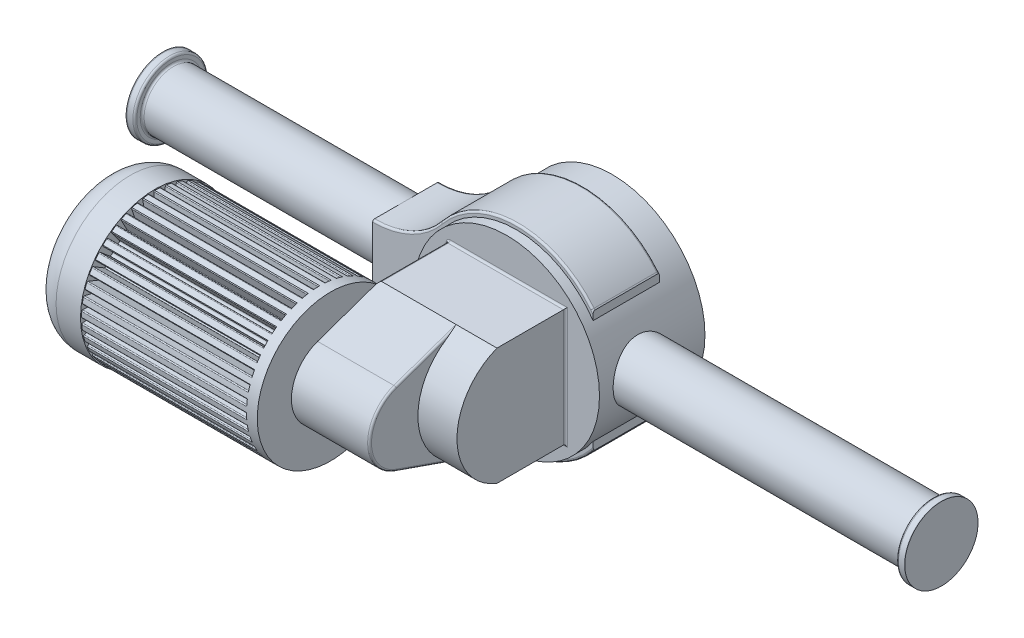
SolidWorks part; units mm, degrees
ref_plane "Front Plane" through (0, 0, 0) normal (0, 0, 1) x (1, 0, 0)
ref_plane "Top Plane" through (0, 0, 0) normal (0, 1, 0) x (1, 0, 0)
ref_plane "Right Plane" through (0, 0, 0) normal (1, 0, 0) x (0, 0, -1)
sketch "Sketch1" plane through (0, 0, 0) normal (0, 0, 1) x (1, 0, 0)
  line L0 (-400, 0) -> (-400, 37.5)
  line L1 (55, 0) -> (-55, 0) construction
  line L2 (-400, 37.5) -> (-390, 37.5)
  line L3 (-390, 37.5) -> (-390, 30)
  line L4 (-390, 30) -> (390, 30)
  line L5 (0, -55) -> (0, 55) construction
  line L6 (390, 37.5) -> (390, 30)
  line L7 (400, 37.5) -> (390, 37.5)
  line L8 (400, 0) -> (400, 37.5)
  line L9 (-87.9629, 0) -> (63.6317, 0) construction
  line L10 (-400, 0) -> (400, 0)
  point P8 (0, 30)
  dimension "D1" = 10
  dimension "D2" = 37.5
  dimension "D3" = 30
  dimension "D4" = 400
revolve "Revolve1" add sketch "Sketch1" angle 360 about L9
sketch "Sketch2" plane through (-400, 0, 0) normal (-1, 0, 0) x (0, 0, 1)
  line L1 (-40, -40) -> (40, -40)
  line L2 (-40, -40) -> (-40, 40)
  line L3 (-40, 40) -> (40, 40)
  line L4 (40, -40) -> (40, 40)
  line L5 (-40, -40) -> (40, 40) construction
  line L6 (-40, 40) -> (40, -40) construction
  point P0 (0, 0)
  dimension "D1" = 80
  dimension "D2" = 80
extrude "Boss-Extrude1" add sketch "Sketch2" along normal blind 10
mirror "Mirror1" about plane through (0, 0, 0) normal (1, 0, 0) of "Boss-Extrude1"
sketch "Sketch3" plane through (0, 0, 0) normal (0, 0, 1) x (1, 0, 0)
  line L0 (44, 0) -> (-44, 0) construction
  line L2 (390, 30) -> (-390, 30) construction
  line L3 (-150, 30) -> (-150, -30)
  line L4 (75.7697, 62.0357) -> (75.7697, -62.0357)
  line L5 (-410, -40) -> (-410, 40) construction
  arc A0 (-80.222, -63.1579) -> (74.8404, -63.1579) centre (-2.6908, 0) ccw
  arc A1 (-150, 30) -> (-80.222, 63.1579) centre (-150, 120) ccw
  arc A2 (74.8404, 63.1579) -> (75.7697, 62.0357) centre (144.6184, 120) ccw
  arc A3 (74.8404, -63.1579) -> (75.7697, -62.0357) centre (144.6184, -120) cw
  arc A4 (-150, -30) -> (-80.222, -63.1579) centre (-150, -120) cw
  arc A5 (74.8404, 63.1579) -> (-80.222, 63.1579) centre (-2.6908, 0) ccw
  point P12 (-80.222, 63.1579)
  point P13 (-150, 30)
  point P20 (75.7697, 0)
  point P25 (-150, 0)
  dimension "D1" = 260
  dimension "D2" = 200
  dimension "D3" = 180
  dimension "D4" = 180
extrude "Boss-Extrude2" add sketch "Sketch3" along normal blind 34 and the other way blind 34 contours A5 A1 L3 A4 A0 A3 L4 A2
sketch "Sketch6" plane through (0, 0, 0) normal (0, 0, 1) x (1, 0, 0)
  circle A0 centre (-2.6908, 0) radius 95
extrude "Boss-Extrude3" add sketch "Sketch6" along normal blind 44 and the other way blind 64
sketch "Sketch7" plane through (0, 0, 0) normal (0, 1, 0) x (1, 0, 0)
  line L0 (115.6, 64) -> (115.6, -44) construction
  line L1 (92.3092, 64) -> (-97.6908, 64) construction
  line L2 (-97.6908, -44) -> (92.3092, -44) construction
  line L3 (115.6, 64) -> (115.6, 89.5157)
  line L4 (115.6, 64) -> (210.6, 64)
  arc A0 (115.6, 89.5157) -> (210.6, 64) centre (115.6, -100.0943) cw
sketch "Sketch8" plane through (0, 0, 44) normal (0, 0, 1) x (1, 0, 0)
  line L1 (-62.6908, -60) -> (57.3092, -60)
  line L2 (-62.6908, -60) -> (-62.6908, 60)
  line L3 (-62.6908, 60) -> (57.3092, 60)
  line L4 (57.3092, -60) -> (57.3092, 60)
  line L5 (-62.6908, -60) -> (57.3092, 60) construction
  line L6 (-62.6908, 60) -> (57.3092, -60) construction
  point P0 (-2.6908, 0)
  dimension "D1" = 120
  dimension "D2" = 120
extrude "Boss-Extrude4" add sketch "Sketch8" along normal blind 70
sketch "Sketch9" plane through (-62.6908, 0, 0) normal (-1, 0, 0) x (0, 0, 1)
  line L0 (114, 60) -> (114, -60)
  arc A0 (114, 60) -> (114, -60) centre (90.5319, 0) cw
extrude "Boss-Extrude5" add sketch "Sketch9" along direction (-1, 0, 0) on the side against the normal up to surface (120 mm away)
sketch "Sketch10" plane through (-62.6908, 0, 0) normal (-1, 0, 0) x (0, 0, 1)
  line L0 (181.4821, 0) -> (-181.4821, 0) construction
  line L1 (114, 60) -> (177.6461, 37.7612)
  line L2 (114, -60) -> (177.6461, -37.7612)
  line L3 (114, 60) -> (114, -60)
  arc A0 (177.6461, -37.7612) -> (177.6461, 37.7612) centre (164.4519, 0) ccw
  dimension "D1" = 40
extrude "Boss-Extrude6" add sketch "Sketch10" against normal blind 80
sketch "Sketch12" plane through (-62.6908, 0, 0) normal (-1, 0, 0) x (0, 0, 1)
  circle A0 centre (164.4519, 0) radius 75
  arc A1 (177.6461, -37.7612) -> (177.6461, 37.7612) centre (164.4519, 0) ccw construction
  dimension "D1" = 150
extrude "Boss-Extrude7" add sketch "Sketch12" along normal blind 180
sketch "Sketch16" plane through (-242.6908, 0, 0) normal (-1, 0, 0) x (0, 0, 1)
  line L3 (165.1686, 74.0313) -> (165.0485, 61.627)
  line L4 (169.9676, 73.8009) -> (168.8566, 61.2216)
  line L5 (164.4519, 75) -> (164.4519, 75.6111)
  line L6 (164.4519, 75.6111) -> (169.6116, 75.2904)
  line L7 (169.6116, 75.2904) -> (171.0517, 75.2904)
  line L8 (171.0517, 75.2904) -> (171.0517, 74.7091)
  line L9 (176.7408, 73.0077) -> (174.6818, 60.7749)
  line L10 (176.1845, 74.0766) -> (176.2801, 74.6802)
  line L11 (176.2801, 74.6802) -> (181.3261, 73.5563)
  line L12 (181.3261, 73.5563) -> (182.7485, 73.331)
  line L13 (182.7485, 73.331) -> (182.6575, 72.7568)
  line L14 (181.4447, 72.0295) -> (178.3795, 59.7788)
  line L15 (188.0105, 70.1864) -> (184.0631, 58.4264)
  line L16 (187.6281, 71.3292) -> (187.817, 71.9105)
  line L17 (187.817, 71.9105) -> (192.6251, 70.011)
  line L18 (192.6251, 70.011) -> (193.9947, 69.566)
  line L19 (193.9947, 69.566) -> (193.815, 69.0131)
  line L20 (192.5034, 68.4844) -> (187.5595, 56.8641)
  line L21 (198.7, 65.6369) -> (192.9616, 54.6392)
  line L22 (198.5012, 66.8255) -> (198.7786, 67.37)
  line L23 (198.7786, 67.37) -> (203.2304, 64.7418)
  line L24 (203.2304, 64.7418) -> (204.5135, 64.088)
  line L25 (204.5135, 64.088) -> (204.2496, 63.57)
  line L26 (202.8713, 63.253) -> (196.1705, 52.5491)
  line L27 (208.5462, 59.4712) -> (201.158, 49.5066)
  line L28 (208.5358, 60.6763) -> (208.895, 61.1707)
  line L29 (208.895, 61.1707) -> (212.8808, 57.8784)
  line L30 (212.8808, 57.8784) -> (214.0458, 57.0319)
  line L31 (214.0458, 57.0319) -> (213.7041, 56.5616)
  line L32 (212.2933, 56.4641) -> (204.0005, 46.9403)
  line L33 (217.3067, 51.8412) -> (208.4506, 43.155)
  line L34 (217.4849, 53.033) -> (217.917, 53.4651)
  line L35 (217.917, 53.4651) -> (221.3387, 49.5899)
  line L36 (221.3387, 49.5899) -> (222.357, 48.5716)
  line L37 (222.357, 48.5716) -> (221.9459, 48.1605)
  line L38 (220.5372, 48.2849) -> (210.8566, 40.1756)
  line L39 (224.7657, 42.9346) -> (214.6599, 35.7407)
  line L40 (225.1281, 44.0839) -> (225.6226, 44.4431)
  line L41 (225.6226, 44.4431) -> (228.3959, 40.0803)
  line L42 (228.3959, 40.0803) -> (229.2424, 38.9152)
  line L43 (229.2424, 38.9152) -> (228.772, 38.5735)
  line L44 (227.4001, 38.9168) -> (216.5702, 32.4217)
  line L45 (230.7396, 32.9709) -> (219.6328, 27.4464)
  line L46 (231.2774, 34.0493) -> (231.8219, 34.3267)
  line L47 (231.8219, 34.3267) -> (233.8786, 29.5838)
  line L48 (233.8786, 29.5838) -> (234.5324, 28.3006)
  line L49 (234.5324, 28.3006) -> (234.0144, 28.0367)
  line L50 (232.713, 28.5904) -> (221.0004, 23.8694)
  line L51 (235.0813, 22.1952) -> (223.247, 18.4763)
  line L52 (235.7811, 23.1763) -> (236.3623, 23.3651)
  line L53 (236.3623, 23.3651) -> (237.6517, 18.3588)
  line L54 (237.6517, 18.3588) -> (238.0967, 16.9892)
  line L55 (238.0967, 16.9892) -> (237.5439, 16.8096)
  line L56 (236.3452, 17.56) -> (224.0382, 14.7294)
  line L57 (237.6838, 10.8731) -> (225.4135, 9.0513)
  line L58 (238.5285, 11.7326) -> (239.1321, 11.8282)
  line L59 (239.1321, 11.8282) -> (239.6225, 6.6818)
  line L60 (239.6225, 6.6818) -> (239.8477, 5.2594)
  line L61 (239.8477, 5.2594) -> (239.2736, 5.1685)
  line L62 (238.207, 6.0972) -> (225.6088, 5.2267)
  line L63 (238.4831, -0.7168) -> (226.0789, -0.5967)
  line L64 (239.4519, 0) -> (240.063, 0)
  line L65 (240.063, 0) -> (239.7423, -5.1597)
  line L66 (239.7423, -5.1597) -> (239.7423, -6.5998)
  line L67 (239.7423, -6.5998) -> (239.1609, -6.5998)
  line L68 (238.2528, -5.5157) -> (225.6735, -4.4047)
  line L69 (237.4596, -12.289) -> (225.2268, -10.2299)
  line L70 (238.5285, -11.7326) -> (239.1321, -11.8282)
  line L71 (239.1321, -11.8282) -> (238.0081, -16.8742)
  line L72 (238.0081, -16.8742) -> (237.7829, -18.2966)
  line L73 (237.7829, -18.2966) -> (237.2087, -18.2056)
  line L74 (236.4813, -16.9928) -> (224.2307, -13.9276)
  line L75 (234.6383, -23.5586) -> (222.8782, -19.6112)
  line L76 (235.7811, -23.1763) -> (236.3623, -23.3651)
  line L77 (236.3623, -23.3651) -> (234.4628, -28.1732)
  line L78 (234.4628, -28.1732) -> (234.0178, -29.5428)
  line L79 (234.0178, -29.5428) -> (233.4649, -29.3632)
  line L80 (232.9363, -28.0515) -> (221.3159, -23.1076)
  line L81 (230.0888, -34.2481) -> (219.091, -28.5097)
  line L82 (231.2774, -34.0493) -> (231.8219, -34.3267)
  line L83 (231.8219, -34.3267) -> (229.1936, -38.7785)
  line L84 (229.1936, -38.7785) -> (228.5398, -40.0616)
  line L85 (228.5398, -40.0616) -> (228.0219, -39.7977)
  line L86 (227.7049, -38.4194) -> (217.001, -31.7186)
  line L87 (223.9231, -44.0943) -> (213.9584, -36.7061)
  line L88 (225.1281, -44.0839) -> (225.6226, -44.4431)
  line L89 (225.6226, -44.4431) -> (222.3302, -48.4289)
  line L90 (222.3302, -48.4289) -> (221.4838, -49.594)
  line L91 (221.4838, -49.594) -> (221.0135, -49.2522)
  line L92 (220.916, -47.8414) -> (211.3922, -39.5486)
  line L93 (216.2931, -52.8548) -> (207.6068, -43.9988)
  line L94 (217.4849, -53.033) -> (217.917, -53.4651)
  line L95 (217.917, -53.4651) -> (214.0417, -56.8868)
  line L96 (214.0417, -56.8868) -> (213.0234, -57.9051)
  line L97 (213.0234, -57.9051) -> (212.6124, -57.4941)
  line L98 (212.7368, -56.0853) -> (204.6275, -46.4048)
  line L99 (207.3865, -60.3138) -> (200.1926, -50.208)
  line L100 (208.5358, -60.6763) -> (208.895, -61.1707)
  line L101 (208.895, -61.1707) -> (204.5321, -63.944)
  line L102 (204.5321, -63.944) -> (203.3671, -64.7905)
  line L103 (203.3671, -64.7905) -> (203.0254, -64.3202)
  line L104 (203.3687, -62.9482) -> (196.8735, -52.1183)
  line L105 (197.4227, -66.2877) -> (191.8983, -55.1809)
  line L106 (198.5012, -66.8255) -> (198.7786, -67.37)
  line L107 (198.7786, -67.37) -> (194.0356, -69.4267)
  line L108 (194.0356, -69.4267) -> (192.7525, -70.0805)
  line L109 (192.7525, -70.0805) -> (192.4886, -69.5625)
  line L110 (193.0423, -68.2612) -> (188.3213, -56.5485)
  line L111 (186.6471, -70.6294) -> (182.9282, -58.7951)
  line L112 (187.6281, -71.3292) -> (187.817, -71.9105)
  line L113 (187.817, -71.9105) -> (182.8107, -73.1999)
  line L114 (182.8107, -73.1999) -> (181.4411, -73.6449)
  line L115 (181.4411, -73.6449) -> (181.2614, -73.092)
  line L116 (182.0119, -71.8933) -> (179.1813, -59.5863)
  line L117 (175.325, -73.2319) -> (173.5031, -60.9616)
  line L118 (176.1845, -74.0766) -> (176.2801, -74.6802)
  line L119 (176.2801, -74.6802) -> (171.1337, -75.1706)
  line L120 (171.1337, -75.1706) -> (169.7113, -75.3959)
  line L121 (169.7113, -75.3959) -> (169.6204, -74.8217)
  line L122 (170.5491, -73.7551) -> (169.6786, -61.1569)
  line L123 (163.7351, -74.0313) -> (163.8552, -61.627)
  line L124 (164.4519, -75) -> (164.4519, -75.6111)
  line L125 (164.4519, -75.6111) -> (159.2921, -75.2904)
  line L126 (159.2921, -75.2904) -> (157.852, -75.2904)
  line L127 (157.852, -75.2904) -> (157.852, -74.7091)
  line L128 (158.9362, -73.8009) -> (160.0472, -61.2216)
  line L129 (152.1629, -73.0077) -> (154.222, -60.7749)
  line L130 (152.7193, -74.0766) -> (152.6237, -74.6802)
  line L131 (152.6237, -74.6802) -> (147.5776, -73.5563)
  line L132 (147.5776, -73.5563) -> (146.1553, -73.331)
  line L133 (146.1553, -73.331) -> (146.2462, -72.7568)
  line L134 (147.4591, -72.0295) -> (150.5242, -59.7788)
  line L135 (140.8933, -70.1864) -> (144.8406, -58.4264)
  line L136 (141.2756, -71.3292) -> (141.0867, -71.9105)
  line L137 (141.0867, -71.9105) -> (136.2786, -70.011)
  line L138 (136.2786, -70.011) -> (134.9091, -69.566)
  line L139 (134.9091, -69.566) -> (135.0887, -69.0131)
  line L140 (136.4004, -68.4844) -> (141.3443, -56.8641)
  line L141 (130.2037, -65.6369) -> (135.9422, -54.6392)
  line L142 (130.4026, -66.8255) -> (130.1251, -67.37)
  line L143 (130.1251, -67.37) -> (125.6734, -64.7418)
  line L144 (125.6734, -64.7418) -> (124.3903, -64.088)
  line L145 (124.3903, -64.088) -> (124.6542, -63.57)
  line L146 (126.0324, -63.253) -> (132.7332, -52.5491)
  line L147 (120.3575, -59.4712) -> (127.7457, -49.5066)
  line L148 (120.368, -60.6763) -> (120.0088, -61.1707)
  line L149 (120.0088, -61.1707) -> (116.023, -57.8784)
  line L150 (116.023, -57.8784) -> (114.8579, -57.0319)
  line L151 (114.8579, -57.0319) -> (115.1996, -56.5616)
  line L152 (116.6105, -56.4641) -> (124.9033, -46.9403)
  line L153 (111.597, -51.8412) -> (120.4531, -43.155)
  line L154 (111.4189, -53.033) -> (110.9867, -53.4651)
  line L155 (110.9867, -53.4651) -> (107.565, -49.5899)
  line L156 (107.565, -49.5899) -> (106.5467, -48.5716)
  line L157 (106.5467, -48.5716) -> (106.9578, -48.1605)
  line L158 (108.3666, -48.2849) -> (118.0471, -40.1756)
  line L159 (104.138, -42.9346) -> (114.2439, -35.7407)
  line L160 (103.7756, -44.0839) -> (103.2812, -44.4431)
  line L161 (103.2812, -44.4431) -> (100.5078, -40.0803)
  line L162 (100.5078, -40.0803) -> (99.6614, -38.9152)
  line L163 (99.6614, -38.9152) -> (100.1317, -38.5735)
  line L164 (101.5036, -38.9168) -> (112.3336, -32.4217)
  line L165 (98.1641, -32.9709) -> (109.2709, -27.4464)
  line L166 (97.6264, -34.0493) -> (97.0819, -34.3267)
  line L167 (97.0819, -34.3267) -> (95.0252, -29.5838)
  line L168 (95.0252, -29.5838) -> (94.3714, -28.3006)
  line L169 (94.3714, -28.3006) -> (94.8894, -28.0367)
  line L170 (96.1907, -28.5904) -> (107.9034, -23.8694)
  line L171 (93.8225, -22.1952) -> (105.6567, -18.4763)
  line L172 (93.1226, -23.1763) -> (92.5414, -23.3651)
  line L173 (92.5414, -23.3651) -> (91.252, -18.3588)
  line L174 (91.252, -18.3588) -> (90.807, -16.9892)
  line L175 (90.807, -16.9892) -> (91.3599, -16.8096)
  line L176 (92.5586, -17.56) -> (104.8656, -14.7294)
  line L177 (91.2199, -10.8731) -> (103.4903, -9.0513)
  line L178 (90.3752, -11.7326) -> (89.7716, -11.8282)
  line L179 (89.7716, -11.8282) -> (89.2813, -6.6818)
  line L180 (89.2813, -6.6818) -> (89.056, -5.2594)
  line L181 (89.056, -5.2594) -> (89.6302, -5.1685)
  line L182 (90.6967, -6.0972) -> (103.295, -5.2267)
  line L183 (90.4206, 0.7168) -> (102.8249, 0.5967)
  line L184 (89.4519, 0) -> (88.8407, 0)
  line L185 (88.8407, 0) -> (89.1615, 5.1597)
  line L186 (89.1615, 5.1597) -> (89.1615, 6.5998)
  line L187 (89.1615, 6.5998) -> (89.7428, 6.5998)
  line L188 (90.651, 5.5157) -> (103.2303, 4.4047)
  line L189 (91.4442, 12.289) -> (103.677, 10.2299)
  line L190 (90.3752, 11.7326) -> (89.7716, 11.8282)
  line L191 (89.7716, 11.8282) -> (90.8956, 16.8742)
  line L192 (90.8956, 16.8742) -> (91.1209, 18.2966)
  line L193 (91.1209, 18.2966) -> (91.695, 18.2056)
  line L194 (92.4224, 16.9928) -> (104.6731, 13.9276)
  line L195 (94.2654, 23.5586) -> (106.0255, 19.6112)
  line L196 (93.1226, 23.1763) -> (92.5414, 23.3651)
  line L197 (92.5414, 23.3651) -> (94.4409, 28.1732)
  line L198 (94.4409, 28.1732) -> (94.8859, 29.5428)
  line L199 (94.8859, 29.5428) -> (95.4388, 29.3632)
  line L200 (95.9675, 28.0515) -> (107.5878, 23.1076)
  line L201 (98.8149, 34.2481) -> (109.8127, 28.5097)
  line L202 (97.6264, 34.0493) -> (97.0819, 34.3267)
  line L203 (97.0819, 34.3267) -> (99.7101, 38.7785)
  line L204 (99.7101, 38.7785) -> (100.3639, 40.0616)
  line L205 (100.3639, 40.0616) -> (100.8819, 39.7977)
  line L206 (101.1989, 38.4194) -> (111.9027, 31.7186)
  line L207 (104.9806, 44.0943) -> (114.9453, 36.7061)
  line L208 (103.7756, 44.0839) -> (103.2812, 44.4431)
  line L209 (103.2812, 44.4431) -> (106.5735, 48.4289)
  line L210 (106.5735, 48.4289) -> (107.4199, 49.594)
  line L211 (107.4199, 49.594) -> (107.8903, 49.2522)
  line L212 (107.9877, 47.8414) -> (117.5116, 39.5486)
  line L213 (112.6107, 52.8548) -> (121.2969, 43.9988)
  line L214 (111.4189, 53.033) -> (110.9867, 53.4651)
  line L215 (110.9867, 53.4651) -> (114.862, 56.8868)
  line L216 (114.862, 56.8868) -> (115.8803, 57.9051)
  line L217 (115.8803, 57.9051) -> (116.2914, 57.4941)
  line L218 (116.1669, 56.0853) -> (124.2763, 46.4048)
  line L219 (121.5173, 60.3138) -> (128.7111, 50.208)
  line L220 (120.368, 60.6763) -> (120.0088, 61.1707)
  line L221 (120.0088, 61.1707) -> (124.3716, 63.944)
  line L222 (124.3716, 63.944) -> (125.5367, 64.7905)
  line L223 (125.5367, 64.7905) -> (125.8784, 64.3202)
  line L224 (125.5351, 62.9482) -> (132.0302, 52.1183)
  line L225 (131.481, 66.2877) -> (137.0054, 55.1809)
  line L226 (130.4026, 66.8255) -> (130.1251, 67.37)
  line L227 (130.1251, 67.37) -> (134.8681, 69.4267)
  line L228 (134.8681, 69.4267) -> (136.1512, 70.0805)
  line L229 (136.1512, 70.0805) -> (136.4152, 69.5625)
  line L230 (135.8615, 68.2612) -> (140.5825, 56.5485)
  line L231 (142.2566, 70.6294) -> (145.9755, 58.7951)
  line L232 (141.2756, 71.3292) -> (141.0867, 71.9105)
  line L233 (141.0867, 71.9105) -> (146.0931, 73.1999)
  line L234 (146.0931, 73.1999) -> (147.4627, 73.6449)
  line L235 (147.4627, 73.6449) -> (147.6423, 73.092)
  line L236 (146.8919, 71.8933) -> (149.7225, 59.5863)
  line L237 (153.5788, 73.2319) -> (155.4006, 60.9616)
  line L238 (152.7193, 74.0766) -> (152.6237, 74.6802)
  line L239 (152.6237, 74.6802) -> (157.7701, 75.1706)
  line L240 (157.7701, 75.1706) -> (159.1924, 75.3959)
  line L241 (159.1924, 75.3959) -> (159.2834, 74.8217)
  line L242 (158.3547, 73.7551) -> (159.2252, 61.1569)
  circle A1 centre (164.4519, 0) radius 75 construction
  arc A3 (165.1686, 74.0313) -> (164.4519, 75) centre (164.1687, 74.0409) ccw
  arc A4 (171.0517, 74.7091) -> (169.9676, 73.8009) centre (170.9637, 73.7129) ccw
  arc A6 (165.0485, 61.627) -> (168.8566, 61.2216) centre (166.948, 61.3812) ccw
  arc A7 (176.7408, 73.0077) -> (176.1845, 74.0766) centre (175.7547, 73.1737) ccw
  arc A8 (182.6575, 72.7568) -> (181.4447, 72.0295) centre (182.4148, 71.7867) ccw
  arc A9 (174.6818, 60.7749) -> (178.3795, 59.7788) centre (176.5194, 60.235) ccw
  arc A10 (188.0105, 70.1864) -> (187.6281, 71.3292) centre (187.0624, 70.5046) ccw
  arc A11 (193.815, 69.0131) -> (192.5034, 68.4844) centre (193.4235, 68.0929) ccw
  arc A12 (184.0631, 58.4264) -> (187.5595, 56.8641) centre (185.7936, 57.6057) ccw
  arc A13 (198.7, 65.6369) -> (198.5012, 66.8255) centre (197.8134, 66.0995) ccw
  arc A14 (204.2496, 63.57) -> (202.8713, 63.253) centre (203.7189, 62.7224) ccw
  arc A15 (192.9616, 54.6392) -> (196.1705, 52.5491) centre (194.5424, 53.5578) ccw
  arc A16 (208.5462, 59.4712) -> (208.5358, 60.6763) centre (207.7429, 60.0668) ccw
  arc A17 (213.7041, 56.5616) -> (212.2933, 56.4641) centre (213.0474, 55.8075) ccw
  arc A18 (201.158, 49.5066) -> (204.0005, 46.9403) centre (202.5502, 48.1913) ccw
  arc A19 (217.3067, 51.8412) -> (217.4849, 53.033) centre (216.6065, 52.5551) ccw
  arc A20 (221.9459, 48.1605) -> (220.5372, 48.2849) centre (221.1793, 47.5184) ccw
  arc A21 (208.4506, 43.155) -> (210.8566, 40.1756) centre (209.6199, 41.6381) ccw
  arc A22 (224.7657, 42.9346) -> (225.1281, 44.0839) centre (224.1858, 43.7493) ccw
  arc A23 (228.772, 38.5735) -> (227.4001, 38.9168) centre (227.9144, 38.0592) ccw
  arc A24 (214.6599, 35.7407) -> (216.5702, 32.4217) centre (215.5775, 34.0596) ccw
  arc A25 (230.7396, 32.9709) -> (231.2774, 34.0493) centre (230.2943, 33.8662) ccw
  arc A26 (234.0144, 28.0367) -> (232.713, 28.5904) centre (233.0869, 27.6629) ccw
  arc A27 (219.6328, 27.4464) -> (221.0004, 23.8694) centre (220.2761, 25.6425) ccw
  arc A28 (235.0813, 22.1952) -> (235.7811, 23.1763) centre (234.7815, 23.1492) ccw
  arc A29 (237.5439, 16.8096) -> (236.3452, 17.56) centre (236.5693, 16.5854) ccw
  arc A30 (223.247, 18.4763) -> (224.0382, 14.7294) centre (223.6002, 16.5939) ccw
  arc A31 (237.6838, 10.8731) -> (238.5285, 11.7326) centre (237.5369, 11.8623) ccw
  arc A32 (239.2736, 5.1685) -> (238.207, 6.0972) centre (238.2759, 5.0996) ccw
  arc A33 (225.4135, 9.0513) -> (225.6088, 5.2267) centre (225.4678, 7.1368) ccw
  arc A34 (238.4831, -0.7168) -> (239.4519, 0) centre (238.4928, 0.2832) ccw
  arc A35 (239.1609, -6.5998) -> (238.2528, -5.5157) centre (238.1648, -6.5118) ccw
  arc A36 (226.0789, -0.5967) -> (225.6735, -4.4047) centre (225.8331, -2.4961) ccw
  arc A37 (237.4596, -12.289) -> (238.5285, -11.7326) centre (237.6255, -11.3028) ccw
  arc A38 (237.2087, -18.2056) -> (236.4813, -16.9928) centre (236.2386, -17.9629) ccw
  arc A39 (225.2268, -10.2299) -> (224.2307, -13.9276) centre (224.6869, -12.0675) ccw
  arc A40 (234.6383, -23.5586) -> (235.7811, -23.1763) centre (234.9565, -22.6106) ccw
  arc A41 (233.4649, -29.3632) -> (232.9363, -28.0515) centre (232.5448, -28.9717) ccw
  arc A42 (222.8782, -19.6112) -> (221.3159, -23.1076) centre (222.0575, -21.3417) ccw
  arc A43 (230.0888, -34.2481) -> (231.2774, -34.0493) centre (230.5514, -33.3615) ccw
  arc A44 (228.0219, -39.7977) -> (227.7049, -38.4194) centre (227.1743, -39.2671) ccw
  arc A45 (219.091, -28.5097) -> (217.001, -31.7186) centre (218.0097, -30.0905) ccw
  arc A46 (223.9231, -44.0943) -> (225.1281, -44.0839) centre (224.5187, -43.2911) ccw
  arc A47 (221.0135, -49.2522) -> (220.916, -47.8414) centre (220.2593, -48.5956) ccw
  arc A48 (213.9584, -36.7061) -> (211.3922, -39.5486) centre (212.6431, -38.0983) ccw
  arc A49 (216.2931, -52.8548) -> (217.4849, -53.033) centre (217.007, -52.1546) ccw
  arc A50 (212.6124, -57.4941) -> (212.7368, -56.0853) centre (211.9702, -56.7275) ccw
  arc A51 (207.6068, -43.9988) -> (204.6275, -46.4048) centre (206.0899, -45.1681) ccw
  arc A52 (207.3865, -60.3138) -> (208.5358, -60.6763) centre (208.2012, -59.7339) ccw
  arc A53 (203.0254, -64.3202) -> (203.3687, -62.9482) centre (202.5111, -63.4626) ccw
  arc A54 (200.1926, -50.208) -> (196.8735, -52.1183) centre (198.5115, -51.1256) ccw
  arc A55 (197.4227, -66.2877) -> (198.5012, -66.8255) centre (198.3181, -65.8424) ccw
  arc A56 (192.4886, -69.5625) -> (193.0423, -68.2612) centre (192.1148, -68.635) ccw
  arc A57 (191.8983, -55.1809) -> (188.3213, -56.5485) centre (190.0943, -55.8242) ccw
  arc A58 (186.6471, -70.6294) -> (187.6281, -71.3292) centre (187.6011, -70.3296) ccw
  arc A59 (181.2614, -73.092) -> (182.0119, -71.8933) centre (181.0373, -72.1174) ccw
  arc A60 (182.9282, -58.7951) -> (179.1813, -59.5863) centre (181.0458, -59.1483) ccw
  arc A61 (175.325, -73.2319) -> (176.1845, -74.0766) centre (176.3141, -73.0851) ccw
  arc A62 (169.6204, -74.8217) -> (170.5491, -73.7551) centre (169.5515, -73.8241) ccw
  arc A63 (173.5031, -60.9616) -> (169.6786, -61.1569) centre (171.5887, -61.016) ccw
  arc A64 (163.7351, -74.0313) -> (164.4519, -75) centre (164.7351, -74.0409) ccw
  arc A65 (157.852, -74.7091) -> (158.9362, -73.8009) centre (157.94, -73.7129) ccw
  arc A66 (163.8552, -61.627) -> (160.0472, -61.2216) centre (161.9558, -61.3812) ccw
  arc A67 (152.1629, -73.0077) -> (152.7193, -74.0766) centre (153.149, -73.1737) ccw
  arc A68 (146.2462, -72.7568) -> (147.4591, -72.0295) centre (146.489, -71.7867) ccw
  arc A69 (154.222, -60.7749) -> (150.5242, -59.7788) centre (152.3844, -60.235) ccw
  arc A70 (140.8933, -70.1864) -> (141.2756, -71.3292) centre (141.8413, -70.5046) ccw
  arc A71 (135.0887, -69.0131) -> (136.4004, -68.4844) centre (135.4802, -68.0929) ccw
  arc A72 (144.8406, -58.4264) -> (141.3443, -56.8641) centre (143.1101, -57.6057) ccw
  arc A73 (130.2037, -65.6369) -> (130.4026, -66.8255) centre (131.0903, -66.0995) ccw
  arc A74 (124.6542, -63.57) -> (126.0324, -63.253) centre (125.1848, -62.7224) ccw
  arc A75 (135.9422, -54.6392) -> (132.7332, -52.5491) centre (134.3614, -53.5578) ccw
  arc A76 (120.3575, -59.4712) -> (120.368, -60.6763) centre (121.1608, -60.0668) ccw
  arc A77 (115.1996, -56.5616) -> (116.6105, -56.4641) centre (115.8563, -55.8075) ccw
  arc A78 (127.7457, -49.5066) -> (124.9033, -46.9403) centre (126.3535, -48.1913) ccw
  arc A79 (111.597, -51.8412) -> (111.4189, -53.033) centre (112.2973, -52.5551) ccw
  arc A80 (106.9578, -48.1605) -> (108.3666, -48.2849) centre (107.7244, -47.5184) ccw
  arc A81 (120.4531, -43.155) -> (118.0471, -40.1756) centre (119.2838, -41.6381) ccw
  arc A82 (104.138, -42.9346) -> (103.7756, -44.0839) centre (104.718, -43.7493) ccw
  arc A83 (100.1317, -38.5735) -> (101.5036, -38.9168) centre (100.9893, -38.0592) ccw
  arc A84 (114.2439, -35.7407) -> (112.3336, -32.4217) centre (113.3263, -34.0596) ccw
  arc A85 (98.1641, -32.9709) -> (97.6264, -34.0493) centre (98.6095, -33.8662) ccw
  arc A86 (94.8894, -28.0367) -> (96.1907, -28.5904) centre (95.8169, -27.6629) ccw
  arc A87 (109.2709, -27.4464) -> (107.9034, -23.8694) centre (108.6276, -25.6425) ccw
  arc A88 (93.8225, -22.1952) -> (93.1226, -23.1763) centre (94.1223, -23.1492) ccw
  arc A89 (91.3599, -16.8096) -> (92.5586, -17.56) centre (92.3344, -16.5854) ccw
  arc A90 (105.6567, -18.4763) -> (104.8656, -14.7294) centre (105.3036, -16.5939) ccw
  arc A91 (91.2199, -10.8731) -> (90.3752, -11.7326) centre (91.3668, -11.8623) ccw
  arc A92 (89.6302, -5.1685) -> (90.6967, -6.0972) centre (90.6278, -5.0996) ccw
  arc A93 (103.4903, -9.0513) -> (103.295, -5.2267) centre (103.4359, -7.1368) ccw
  arc A94 (90.4206, 0.7168) -> (89.4519, 0) centre (90.4109, -0.2832) ccw
  arc A95 (89.7428, 6.5998) -> (90.651, 5.5157) centre (90.7389, 6.5118) ccw
  arc A96 (102.8249, 0.5967) -> (103.2303, 4.4047) centre (103.0707, 2.4961) ccw
  arc A97 (91.4442, 12.289) -> (90.3752, 11.7326) centre (91.2782, 11.3028) ccw
  arc A98 (91.695, 18.2056) -> (92.4224, 16.9928) centre (92.6651, 17.9629) ccw
  arc A99 (103.677, 10.2299) -> (104.6731, 13.9276) centre (104.2169, 12.0675) ccw
  arc A100 (94.2654, 23.5586) -> (93.1226, 23.1763) centre (93.9472, 22.6106) ccw
  arc A101 (95.4388, 29.3632) -> (95.9675, 28.0515) centre (96.359, 28.9717) ccw
  arc A102 (106.0255, 19.6112) -> (107.5878, 23.1076) centre (106.8462, 21.3417) ccw
  arc A103 (98.8149, 34.2481) -> (97.6264, 34.0493) centre (98.3523, 33.3615) ccw
  arc A104 (100.8819, 39.7977) -> (101.1989, 38.4194) centre (101.7295, 39.2671) ccw
  arc A105 (109.8127, 28.5097) -> (111.9027, 31.7186) centre (110.894, 30.0905) ccw
  arc A106 (104.9806, 44.0943) -> (103.7756, 44.0839) centre (104.385, 43.2911) ccw
  arc A107 (107.8903, 49.2522) -> (107.9877, 47.8414) centre (108.6444, 48.5956) ccw
  arc A108 (114.9453, 36.7061) -> (117.5116, 39.5486) centre (116.2606, 38.0983) ccw
  arc A109 (112.6107, 52.8548) -> (111.4189, 53.033) centre (111.8968, 52.1546) ccw
  arc A110 (116.2914, 57.4941) -> (116.1669, 56.0853) centre (116.9335, 56.7275) ccw
  arc A111 (121.2969, 43.9988) -> (124.2763, 46.4048) centre (122.8138, 45.1681) ccw
  arc A112 (121.5173, 60.3138) -> (120.368, 60.6763) centre (120.7026, 59.7339) ccw
  arc A113 (125.8784, 64.3202) -> (125.5351, 62.9482) centre (126.3927, 63.4626) ccw
  arc A114 (128.7111, 50.208) -> (132.0302, 52.1183) centre (130.3923, 51.1256) ccw
  arc A115 (131.481, 66.2877) -> (130.4026, 66.8255) centre (130.5857, 65.8424) ccw
  arc A116 (136.4152, 69.5625) -> (135.8615, 68.2612) centre (136.789, 68.635) ccw
  arc A117 (137.0054, 55.1809) -> (140.5825, 56.5485) centre (138.8094, 55.8242) ccw
  arc A118 (142.2566, 70.6294) -> (141.2756, 71.3292) centre (141.3026, 70.3296) ccw
  arc A119 (147.6423, 73.092) -> (146.8919, 71.8933) centre (147.8664, 72.1174) ccw
  arc A120 (145.9755, 58.7951) -> (149.7225, 59.5863) centre (147.858, 59.1483) ccw
  arc A121 (153.5788, 73.2319) -> (152.7193, 74.0766) centre (152.5896, 73.0851) ccw
  arc A122 (159.2834, 74.8217) -> (158.3547, 73.7551) centre (159.3523, 73.8241) ccw
  arc A123 (155.4006, 60.9616) -> (159.2252, 61.1569) centre (157.3151, 61.016) ccw
  point P0 (164.4519, 0)
  point P486 (164.4519, 0)
  dimension "D1" = 2
  dimension "D2" = 2
  dimension "D3" = 40
extrude "Cut-Extrude1" cut sketch "Sketch16" against normal blind 169
sketch "Sketch15" plane through (-242.6908, 0, 0) normal (-1, 0, 0) x (0, 0, 1)
  circle A0 centre (164.4519, 0) radius 76
  circle A1 centre (164.4519, 0) radius 75 construction
  dimension "D1" = 152
extrude "Boss-Extrude8" add sketch "Sketch15" along normal blind 50
fillet "Fillet2" radius 25 1 edges at (-292.6908, 0, 240.4519)
fillet "Fillet5" radius 2 18 edges at (75.3028, 62.5949, -34) (-111.3722, -38.711, -34) (-2.6908, -100, -34) (75.3028, -62.5949, 34) (-2.6908, -100, 34) (-2.6908, 100, -34) (-2.6908, 100, 34) (75.3028, -62.5949, -34) (75.3028, 62.5949, 34) (400, 0, 37.5) (390, 0, 30) (390, 0, 37.5) (-111.3722, -38.711, 34) (-111.3722, 38.711, 34) (-111.3722, 38.711, -34) (-390, 0, 30) (-390, 0, 37.5) (-400, 0, 37.5)
fillet "Fillet11" radius 2 1 edges at (-62.6908, 60, 79)
fillet "Fillet10" radius 2 5 edges at (-62.6908, -1, 44) (-1.6908, 60, 44) (57.3092, 0, 44) (-2.6908, -60, 44) (-62.105, 59.4142, 44)
fillet "Fillet12" radius 2 3 edges at (17.3092, 48.8806, 145.8231) (17.3092, -48.8806, 145.8231) (17.3092, 0, 204.4519)
sketch "Sketch17" plane through (0, 0, 0) normal (0, 1, 0) x (1, 0, 0)
  line L1 (-398.7382, 46.088) -> (-416.3541, 46.088)
  line L2 (-398.7382, 46.088) -> (-398.7382, -47.2712)
  line L3 (-398.7382, -47.2712) -> (-416.3541, -47.2712)
  line L4 (-416.3541, 46.088) -> (-416.3541, -47.2712)
  line L5 (398.4158, 43.4238) -> (412.2563, 43.4238)
  line L6 (398.4158, 43.4238) -> (398.4158, -47.2712)
  line L7 (398.4158, -47.2712) -> (412.2563, -47.2712)
  line L8 (412.2563, 43.4238) -> (412.2563, -47.2712)
extrude "Cut-Extrude2" cut sketch "Sketch17" against normal blind 50 and the other way blind 50
